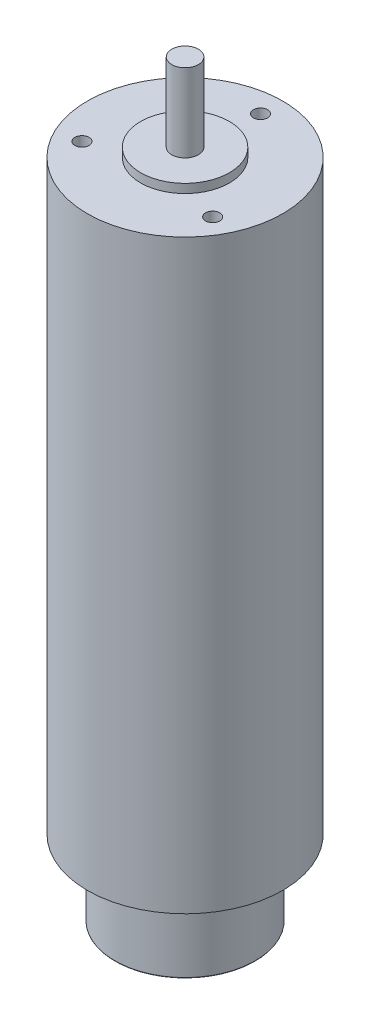
SolidWorks part; units mm, degrees
ref_plane "정면" through (0, 0, 0) normal (0, 0, 1) x (1, 0, 0)
ref_plane "윗면" through (0, 0, 0) normal (0, 1, 0) x (1, 0, 0)
ref_plane "우측면" through (0, 0, 0) normal (1, 0, 0) x (0, 0, -1)
sketch "스케치1" plane through (0, 0, 0) normal (0, 1, 0) x (1, 0, 0)
  circle A0 centre (0, 0) radius 11
  dimension "D1" = 22
extrude "보스-돌출1" add sketch "스케치1" along normal blind 66
sketch "스케치2" plane through (0, 66, 0) normal (0, 1, 0) x (1, 0, 0)
  circle A0 centre (0, 0) radius 5
  dimension "D1" = 10
extrude "보스-돌출2" add sketch "스케치2" along normal blind 1 separate body
sketch "스케치3" plane through (0, 67, 0) normal (0, 1, 0) x (1, 0, 0)
  circle A0 centre (0, 0) radius 1.5
  dimension "D1" = 3
extrude "보스-돌출3" add sketch "스케치3" along normal blind 8.8 separate body
sketch "스케치4" plane through (0, 0, 0) normal (0, -1, 0) x (1, 0, 0)
  circle A0 centre (0, 0) radius 7.9
  dimension "D1" = 15.8
extrude "보스-돌출4" add sketch "스케치4" along normal blind 8.5 separate body
fillet "필렛2" radius 0.1 1 edges at (0, -8.5, -7.9)
sketch "스케치5" plane through (0, 75.8, 0) normal (0, 1, 0) x (1, 0, 0)
  line L1 (-3.1841, 3.5344) -> (3.6784, 3.5344)
  line L2 (-3.1841, 3.5344) -> (-3.1841, 1)
  line L3 (-3.1841, 1) -> (3.6784, 1)
  line L4 (3.6784, 3.5344) -> (3.6784, 1)
  circle A0 centre (0, 0) radius 1.5 construction
  dimension "D1" = 1
hole_wizard "M2 나사 구멍1" positions "스케치6" profile "스케치8" tap size "M2" standard "ISO"
sketch "스케치6" plane through (0, 66, 0) normal (0, 1, 0) x (1, 0, 0)
  circle A0 centre (0, 0) radius 5 construction
  point P0 (0, 8.5)
  dimension "D1" = 8.5
sketch "스케치8" plane through (0, 66, -8.5) normal (1, 0, 0) x (0, 0, 1)
  line L0 (0, 0) -> (0, 5.4807)
  line L1 (0, 5.4807) -> (0.8, 5)
  line L2 (0.8, 5) -> (0.8, 0)
  line L5 (0.8, 0) -> (0, 0)
  line L10 (0, 5.4807) -> (-0.8, 5) construction
  line L11 (0, -6.35) -> (0, 107.95) construction
  dimension "탭 드릴 지름" = 1.6
  dimension "탭 드릴 깊이" = 5
  dimension "드릴 각도" = 118
cosmetic thread "구멍 나사산1" parameters "D1"=4, "D2"=2
pattern_circular "원형 패턴2" count 3 every 120 about axis through (0, 66, 0) along (0, 1, 0) of "M2 나사 구멍1"
sketch "Эскиз1" plane through (0, 66, 0) normal (0, 1, 0) x (1, 0, 0)
  circle A0 centre (0, 0) radius 8.5
  circle A3 centre (7.3612, -4.25) radius 0.8
  circle A4 centre (7.3612, -4.25) radius 0.8 construction
